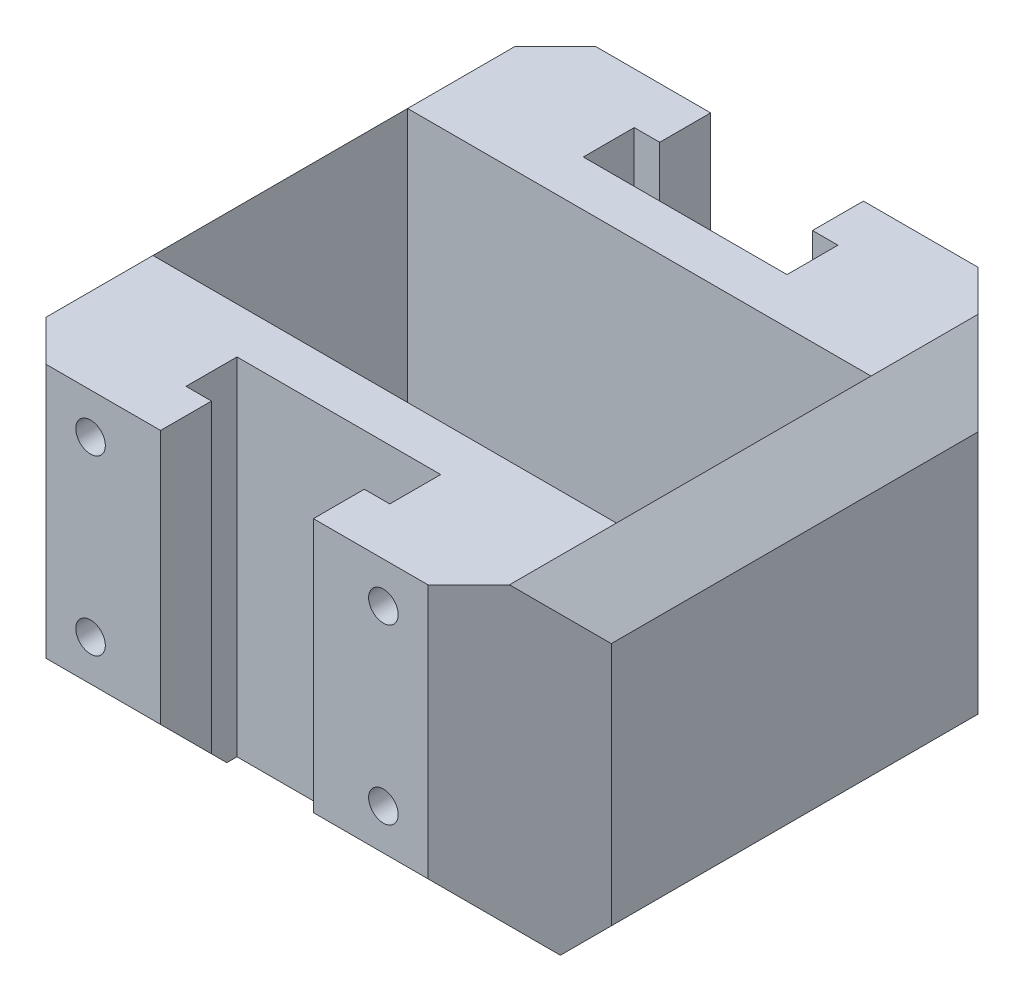
SolidWorks part; units mm, degrees
ref_plane "Front Plane" through (0, 0, 0) normal (0, 0, 1) x (1, 0, 0)
ref_plane "Top Plane" through (0, 0, 0) normal (0, 1, 0) x (1, 0, 0)
ref_plane "Right Plane" through (0, 0, 0) normal (1, 0, 0) x (0, 0, -1)
sketch "Sketch1" plane through (0, 0, 0) normal (0, 1, 0) x (1, 0, 0)
  line L0 (-27.75, -17.5) -> (-27.75, 17.5)
  line L1 (-22.75, -12.5) -> (22.75, -12.5)
  line L2 (-22.75, -12.5) -> (-22.75, 12.5)
  line L3 (-22.75, 12.5) -> (22.75, 12.5)
  line L4 (22.75, -12.5) -> (22.75, 12.5)
  line L5 (-22.75, -12.5) -> (22.75, 12.5) construction
  line L6 (-22.75, 12.5) -> (22.75, -12.5) construction
  line L7 (-27.75, 17.5) -> (27.75, 17.5)
  line L8 (27.75, -17.5) -> (27.75, 17.5)
  line L9 (-27.75, -17.5) -> (27.75, -17.5)
  point P0 (0, 0)
  dimension "D1" = 45.5
  dimension "D2" = 25
  dimension "D3" = 5
extrude "Boss-Extrude1" add sketch "Sketch1" along normal blind 28
sketch "Sketch2" plane through (0, 0, 0) normal (0, -1, 0) x (1, 0, 0)
  line L0 (-27.75, 17.5) -> (27.75, 17.5) construction
  line L1 (-27.75, 17.5) -> (27.75, 17.5)
  line L2 (-27.75, -17.5) -> (-27.75, 17.5) construction
  line L3 (27.75, -17.5) -> (-27.75, -17.5) construction
  line L4 (27.75, 17.5) -> (27.75, -17.5) construction
  line L5 (-27.75, -17.5) -> (-27.75, 17.5)
  line L6 (27.75, -17.5) -> (-27.75, -17.5)
  line L7 (27.75, 17.5) -> (27.75, -17.5)
extrude "Boss-Extrude2" add sketch "Sketch2" along normal blind 6
sketch "Sketch4" plane through (0, 0, 0) normal (0, 1, 0) x (1, 0, 0)
  line L0 (22.75, -12.5) -> (22.75, 12.5) construction
  line L1 (-4.2, -10.25) -> (20.25, -10.25) construction
  line L2 (-4.2, -10.25) -> (-4.2, 10.25) construction
  line L3 (-4.2, 10.25) -> (20.25, 10.25) construction
  line L4 (20.25, -10.25) -> (20.25, 10.25) construction
  line L5 (-4.2, -10.25) -> (20.25, 10.25) construction
  line L6 (-4.2, 10.25) -> (20.25, -10.25) construction
  circle A0 centre (-4.2, 10.25) radius 1
  circle A1 centre (20.25, 10.25) radius 1
  circle A2 centre (20.25, -10.25) radius 1
  circle A3 centre (-4.2, -10.25) radius 1
  point P0 (8.025, 0)
  point P11 (0, 0)
  dimension "D1" = 2
  dimension "D2" = 20.5
  dimension "D3" = 24.45
  dimension "D4" = 2.5
extrude "Cut-Extrude1" cut sketch "Sketch4" against normal blind 3.5
sketch "Sketch5" plane through (0, -3.5, 0) normal (0, 1, 0) x (1, 0, 0)
  circle A0 centre (-4.2, 10.25) radius 2
  circle A1 centre (20.25, 10.25) radius 2
  circle A2 centre (20.25, -10.25) radius 2
  circle A3 centre (-4.2, -10.25) radius 2
  dimension "D1" = 4
extrude "Cut-Extrude2" cut sketch "Sketch5" against normal up to next
sketch "Sketch6" plane through (0, 0, 0) normal (0, 1, 0) x (1, 0, 0)
  line L1 (-1.75, -11.25) -> (17.5, -11.25)
  line L2 (-1.75, -11.25) -> (-1.75, 11.25)
  line L3 (-1.75, 11.25) -> (17.5, 11.25)
  line L4 (17.5, -11.25) -> (17.5, 11.25)
  line L5 (-1.75, -11.25) -> (17.5, 11.25) construction
  line L6 (-1.75, 11.25) -> (17.5, -11.25) construction
  circle A0 centre (20.25, 10.25) radius 1 construction
  point P0 (7.875, 0)
  point P5 (0, 0)
  point P7 (8.3709, 0)
  dimension "D1" = 22.5
  dimension "D2" = 19.25
  dimension "D3" = 2.75
extrude "Cut-Extrude3" cut sketch "Sketch6" against normal up to next
chamfer "Chamfer1" distance 1.5 angle 45 4 edges at (-1.75, -3, 11.25) (17.5, -3, 11.25) (-1.75, -3, -11.25) (17.5, -3, -11.25)
sketch "Sketch7" plane through (0, 0, 0) normal (0, 1, 0) x (1, 0, 0)
  line L0 (-1.75, 9.75) -> (-1.75, -9.75) construction
  circle A0 centre (-12.5, 0) radius 3
  point P4 (0, 0)
  dimension "D1" = 6
  dimension "D2" = 10.75
extrude "Cut-Extrude4" cut sketch "Sketch7" against normal up to next
chamfer "Chamfer2" distance 1 angle 45 2 edges at (-12.5, -6, 3) (-12.5, 0, 3)
sketch "Sketch8" plane through (0, 28, 0) normal (0, 1, 0) x (1, 0, 0)
  line L6 (27.75, -17.5) -> (27.75, 17.5) construction
  line L7 (-27.75, -17.5) -> (27.75, -17.5)
  line L8 (-27.75, -17.5) -> (-27.75, -27)
  line L9 (-27.75, -27) -> (27.75, -27)
  line L10 (27.75, -17.5) -> (27.75, -27)
  dimension "D1" = 9.5
extrude "Boss-Extrude3" add sketch "Sketch8" against normal up to surface (34 mm away) up to face at (-12.5, -6, 4)
sketch "Sketch10" plane through (0, 28, 0) normal (0, 1, 0) x (1, 0, 0)
  line L0 (-27.75, -27) -> (27.75, -27) construction
  line L1 (-10, -17) -> (10, -17)
  line L2 (-10, -17) -> (-10, -22)
  line L3 (-10, -22) -> (10, -22)
  line L4 (10, -17) -> (10, -22)
  line L5 (-10, -17) -> (10, -22) construction
  line L6 (-10, -22) -> (10, -17) construction
  line L7 (-7.5, -27) -> (7.5, -27)
  line L8 (-7.5, -27) -> (-7.5, -22)
  line L9 (-7.5, -22) -> (7.5, -22)
  line L10 (7.5, -27) -> (7.5, -22)
  line L11 (-7.5, -27) -> (7.5, -22) construction
  line L12 (-7.5, -22) -> (7.5, -27) construction
  point P0 (0, -19.5)
  point P5 (0, -24.5)
  point P12 (0, 0)
  point P13 (0, 0)
  point P15 (-7.5, -24.5)
  line M10 (-27.75, -27) -> (27.75, -27)
  dimension "D1" = 5
  dimension "D2" = 20
  dimension "D3" = 15
extrude "Cut-Extrude5" cut sketch "Sketch10" against normal up to next contours L4 L1 L2 L3 | L10 L3 L8 M10 region at (0, 28, 19.5) region at (0, 28, 24.5)
mirror "Mirror3" about plane through (0, 0, 0) normal (0, 0, 1) of "Cut-Extrude5", "Boss-Extrude3"
chamfer "Chamfer7" distance 9 angle 45 8 edges at (17.625, -6, -27) (27.75, 11, -27) (-17.625, -6, -27) (-27.75, 11, -27) (17.625, -6, 27) (27.75, 11, 27) (-17.625, -6, 27) (-27.75, 11, 27)
chamfer "Chamfer8" distance 5 angle 45 2 edges at (27.75, 28, 0) (-27.75, 28, 0)
chamfer "Chamfer9" distance 5 angle 45 2 edges at (27.75, -6, 0) (-27.75, -6, 0)
sketch "Sketch12" plane through (0, 0, -27) normal (0, 0, -1) x (-1, 0, 0)
  line L0 (18.75, 28) -> (7.5, 28) construction
  line L1 (-14.375, 7) -> (14.375, 7) construction
  line L2 (-14.375, 7) -> (-14.375, 24) construction
  line L3 (-14.375, 24) -> (14.375, 24) construction
  line L4 (14.375, 7) -> (14.375, 24) construction
  line L5 (-14.375, 7) -> (14.375, 24) construction
  line L6 (-14.375, 24) -> (14.375, 7) construction
  line L7 (7.5, 3) -> (18.75, 3) construction
  circle A0 centre (-14.375, 24) radius 1.45
  circle A1 centre (14.375, 24) radius 1.45
  circle A2 centre (14.375, 7) radius 1.45
  circle A3 centre (-14.375, 7) radius 1.45
  point P0 (0, 15.5)
  point P13 (0, 0)
  dimension "D1" = 2.9
  dimension "D3" = 4
  dimension "D4" = 4
  dimension "D2" = 28.75
extrude "Cut-Extrude7" cut sketch "Sketch12" against normal blind 8
mirror "Mirror4" about plane through (0, 0, 0) normal (0, 0, 1) of "Cut-Extrude7"
